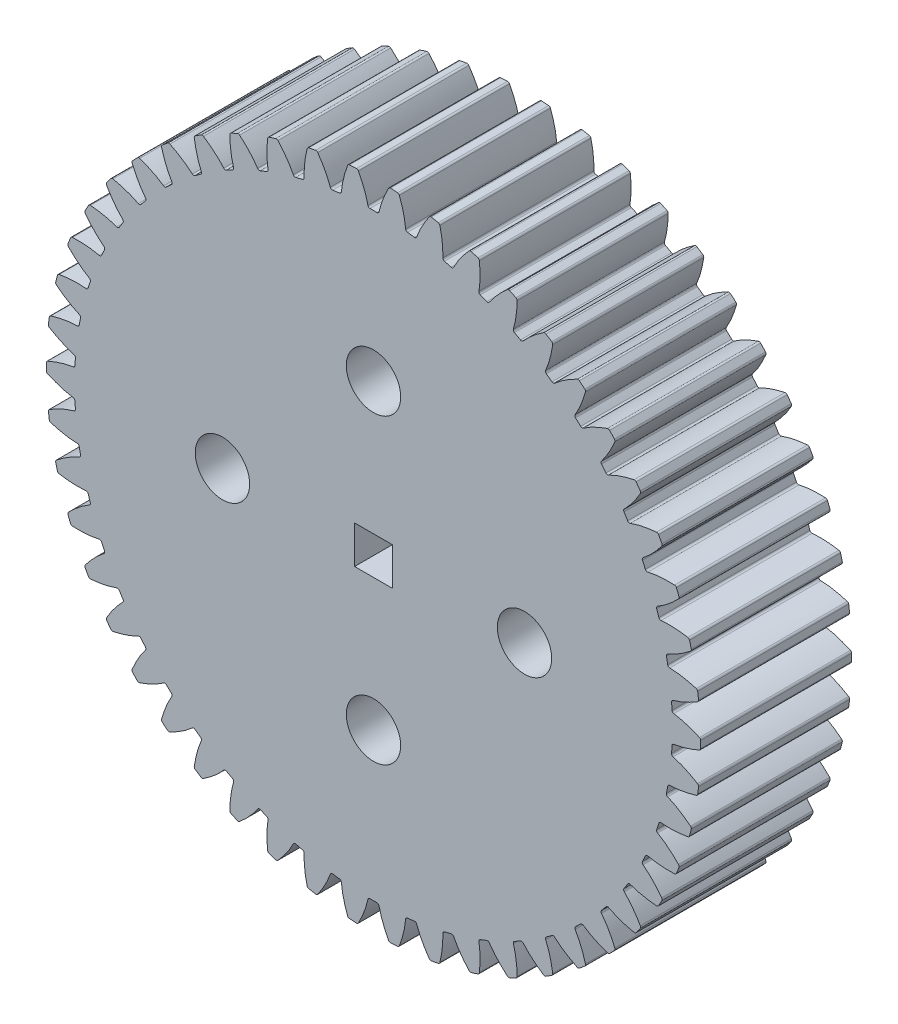
SolidWorks part; units mm, degrees
material "Alloy Steel"
ref_plane "Front" through (0, 0, 0) normal (0, 0, 1) x (1, 0, 0)
ref_plane "Top" through (0, 0, 0) normal (0, 1, 0) x (1, 0, 0)
ref_plane "Right" through (0, 0, 0) normal (1, 0, 0) x (0, 0, -1)
sketch "Sketch1" plane through (0, 0, 0) normal (0, 0, 1) x (1, 0, 0)
  circle A0 centre (0, 0) radius 27.5167
  dimension "OutsideDiameter" = 55.0333
extrude "Boss-Extrude1" add sketch "Sketch1" along normal blind 12.7
sketch "Sketch3" plane through (0, 0, 0) normal (0, 0, 1) x (1, 0, 0)
  line L0 (0, 0) -> (43.7181, 0) construction
  line L2 (0, 0) -> (-0.415, 25.132) construction
  line L3 (0, 0) -> (0.415, 25.132) construction
  line L4 (0.415, 25.132) -> (0.4105, 24.8593) construction
  line L5 (0, 0) -> (0, 61.276) construction
  line L6 (-0.415, 25.132) -> (-0.4105, 24.8593) construction
  circle A0 centre (0, 0) radius 27.5167 construction
  circle A1 centre (0, 0) radius 26.4583 construction
  circle A2 centre (0, 0) radius 24.8627 construction
  arc A3 (0.415, 25.132) -> (-0.415, 25.132) centre (0, 0) ccw construction
  arc A5 (1.3181, 27.4851) -> (-1.3181, 27.4851) centre (0, 0) ccw
  spline S0 degree 4 poles (-0.4105, 24.8593) (-0.4106, 24.8634) (-0.411, 24.875) (-0.4124, 24.8969) (-0.4153, 24.9326) (-0.42, 24.9781) (-0.4274, 25.0369) (-0.4376, 25.1061) (-0.4505, 25.182) (-0.4663, 25.2646) (-0.4836, 25.347) (-0.5023, 25.4291) (-0.5223, 25.5108) (-0.5481, 25.6097) (-0.5811, 25.7281) (-0.6229, 25.8665) (-0.674, 26.0231) (-0.7301, 26.1825) (-0.7886, 26.3392) (-0.8515, 26.4973) (-0.915, 26.65) (-0.9848, 26.8084) (-1.0512, 26.9545) (-1.13, 27.1178) (-1.1947, 27.2495) (-1.2847, 27.4229) (-1.3393, 27.5252) (-1.4047, 27.6448) (-1.4345, 27.6978) (-1.4529, 27.7305) knots 0 0 0 0 0 0.005377 0.015084 0.028532 0.04661 0.064855 0.092111 0.119476 0.146842 0.174209 0.201575 0.228941 0.256307 0.307035 0.361767 0.4165 0.471232 0.525964 0.580697 0.635429 0.690161 0.744894 0.799626 0.854358 0.909091 0.954545 1 1 1 1 1 construction
  spline S1 degree 4 poles (-0.4105, 24.8593) (-0.4106, 24.8634) (-0.411, 24.875) (-0.4124, 24.8969) (-0.4153, 24.9326) (-0.42, 24.9781) (-0.4274, 25.0369) (-0.4376, 25.1061) (-0.4505, 25.182) (-0.4663, 25.2646) (-0.4836, 25.347) (-0.5023, 25.4291) (-0.5223, 25.5108) (-0.5481, 25.6097) (-0.5811, 25.7281) (-0.6229, 25.8665) (-0.674, 26.0231) (-0.7301, 26.1825) (-0.7886, 26.3392) (-0.8515, 26.4973) (-0.915, 26.65) (-0.9848, 26.8084) (-1.0512, 26.9545) (-1.13, 27.1178) (-1.1947, 27.2495) (-1.2652, 27.3853) (-1.3001, 27.4513) (-1.3181, 27.4851) knots 0 0 0 0 0 0.005377 0.015084 0.028532 0.04661 0.064855 0.092111 0.119476 0.146842 0.174209 0.201575 0.228941 0.256307 0.307035 0.361767 0.4165 0.471232 0.525964 0.580697 0.635429 0.690161 0.744894 0.799626 0.854358 0.909091 0.909091 0.909091 0.909091 0.909091
  spline S2 degree 4 poles (0.4105, 24.8593) (0.4106, 24.8634) (0.411, 24.875) (0.4124, 24.8969) (0.4153, 24.9326) (0.42, 24.9781) (0.4274, 25.0369) (0.4376, 25.1061) (0.4505, 25.182) (0.4663, 25.2646) (0.4836, 25.347) (0.5023, 25.4291) (0.5223, 25.5108) (0.5481, 25.6097) (0.5811, 25.7281) (0.6229, 25.8665) (0.674, 26.0231) (0.7301, 26.1825) (0.7886, 26.3392) (0.8515, 26.4973) (0.915, 26.65) (0.9848, 26.8084) (1.0512, 26.9545) (1.13, 27.1178) (1.1947, 27.2495) (1.2847, 27.4229) (1.3393, 27.5252) (1.4047, 27.6448) (1.4345, 27.6978) (1.4529, 27.7305) knots 0 0 0 0 0 0.005377 0.015084 0.028532 0.04661 0.064855 0.092111 0.119476 0.146842 0.174209 0.201575 0.228941 0.256307 0.307035 0.361767 0.4165 0.471232 0.525964 0.580697 0.635429 0.690161 0.744894 0.799626 0.854358 0.909091 0.954545 1 1 1 1 1 construction
  spline S3 degree 4 poles (0.4105, 24.8593) (0.4106, 24.8634) (0.411, 24.875) (0.4124, 24.8969) (0.4153, 24.9326) (0.42, 24.9781) (0.4274, 25.0369) (0.4376, 25.1061) (0.4505, 25.182) (0.4663, 25.2646) (0.4836, 25.347) (0.5023, 25.4291) (0.5223, 25.5108) (0.5481, 25.6097) (0.5811, 25.7281) (0.6229, 25.8665) (0.674, 26.0231) (0.7301, 26.1825) (0.7886, 26.3392) (0.8515, 26.4973) (0.915, 26.65) (0.9848, 26.8084) (1.0512, 26.9545) (1.13, 27.1178) (1.1947, 27.2495) (1.2652, 27.3853) (1.3001, 27.4513) (1.3181, 27.4851) knots 0 0 0 0 0 0.005377 0.015084 0.028532 0.04661 0.064855 0.092111 0.119476 0.146842 0.174209 0.201575 0.228941 0.256307 0.307035 0.361767 0.4165 0.471232 0.525964 0.580697 0.635429 0.690161 0.744894 0.799626 0.854358 0.909091 0.909091 0.909091 0.909091 0.909091
  point P0 (0, 25.1354)
  dimension "OutsideDiameter" = 55.0333
  dimension "PitchCircle" = 52.9167
  dimension "BaseCircle" = 49.7254
  dimension "DedendumCircle" = 50.2708
sketch "DCLTBC" [suppressed] plane through (0, 0, 0) normal (0, 0, 1) x (1, 0, 0)
  line L0 (0, 0) -> (41.04, 0) construction
  line L1 (-0.5092, 17.7198) -> (-0.5142, 17.8938) construction
  line L2 (0.5092, 17.7198) -> (0.5142, 17.8938) construction
  line L3 (-0.5092, 17.7198) -> (-0.5142, 17.8938)
  line L4 (0.5092, 17.7198) -> (0.5142, 17.8938)
  line L5 (0, 0) -> (0, 104.9356) construction
  circle A0 centre (0, 0) radius 20.1083
  circle A1 centre (0, 0) radius 19.05 construction
  circle A2 centre (0, 0) radius 17.9011 construction
  arc A3 (0.5092, 17.7198) -> (-0.5092, 17.7198) centre (0, 0) ccw construction
  arc A4 (0.5092, 17.7198) -> (-0.5092, 17.7198) centre (0, 0) ccw
  spline S0 degree 4 poles (-999.1216, -34.2256) (-11.697, 16.348) (-0.6508, 17.0677) (-0.4759, 17.5158) (-0.5192, 17.9552) (-0.5239, 17.9932) (-0.5311, 18.0423) (-0.541, 18.1001) (-0.5533, 18.1635) (-0.5683, 18.2324) (-0.5847, 18.3009) (-0.6024, 18.3693) (-0.6212, 18.4372) (-0.6453, 18.5194) (-0.6762, 18.6178) (-0.7152, 18.7324) (-0.7627, 18.8621) (-0.8147, 18.9939) (-0.8688, 19.1232) (-0.9269, 19.2534) (-0.9855, 19.3791) (-1.0497, 19.5092) (-1.1108, 19.629) (-1.1831, 19.7627) (-1.4901, 20.3193) (-2.6416, 22.1387) (11.7833, -2.0901) (-516.0573, 877.426) knots -0.638399 -0.638399 -0.638399 -0.638399 -0.638399 0.005377 0.015084 0.028532 0.04661 0.064855 0.092111 0.119476 0.146842 0.174209 0.201575 0.228941 0.256307 0.307035 0.361767 0.4165 0.471232 0.525964 0.580697 0.635429 0.690161 0.744894 0.799626 0.854358 1.821345 1.821345 1.821345 1.821345 1.821345 only from (-0.5142, 17.8938) to (-1.3554, 20.0626) construction
  spline S1 degree 4 poles (999.1216, -34.2256) (11.697, 16.348) (0.6508, 17.0677) (0.4759, 17.5158) (0.5192, 17.9552) (0.5239, 17.9932) (0.5311, 18.0423) (0.541, 18.1001) (0.5533, 18.1635) (0.5683, 18.2324) (0.5847, 18.3009) (0.6024, 18.3693) (0.6212, 18.4372) (0.6453, 18.5194) (0.6762, 18.6178) (0.7152, 18.7324) (0.7627, 18.8621) (0.8147, 18.9939) (0.8688, 19.1232) (0.9269, 19.2534) (0.9855, 19.3791) (1.0497, 19.5092) (1.1108, 19.629) (1.1831, 19.7627) (1.4901, 20.3193) (2.6416, 22.1387) (-11.7833, -2.0901) (516.0573, 877.426) knots -0.638399 -0.638399 -0.638399 -0.638399 -0.638399 0.005377 0.015084 0.028532 0.04661 0.064855 0.092111 0.119476 0.146842 0.174209 0.201575 0.228941 0.256307 0.307035 0.361767 0.4165 0.471232 0.525964 0.580697 0.635429 0.690161 0.744894 0.799626 0.854358 1.821345 1.821345 1.821345 1.821345 1.821345 only from (0.5142, 17.8938) to (1.3554, 20.0626) construction
  spline S2 degree 4 poles (-0.5142, 17.8938) (-0.5143, 17.8972) (-0.5148, 17.9069) (-0.5163, 17.9253) (-0.5192, 17.9552) (-0.5239, 17.9932) (-0.5311, 18.0423) (-0.541, 18.1001) (-0.5533, 18.1635) (-0.5683, 18.2324) (-0.5847, 18.3009) (-0.6024, 18.3693) (-0.6212, 18.4372) (-0.6453, 18.5194) (-0.6762, 18.6178) (-0.7152, 18.7324) (-0.7627, 18.8621) (-0.8147, 18.9939) (-0.8688, 19.1232) (-0.9269, 19.2534) (-0.9855, 19.3791) (-1.0497, 19.5092) (-1.1108, 19.629) (-1.1831, 19.7627) (-1.2425, 19.8704) (-1.307, 19.9812) (-1.3389, 20.0351) (-1.3554, 20.0626) knots 0 0 0 0 0 0.005377 0.015084 0.028532 0.04661 0.064855 0.092111 0.119476 0.146842 0.174209 0.201575 0.228941 0.256307 0.307035 0.361767 0.4165 0.471232 0.525964 0.580697 0.635429 0.690161 0.744894 0.799626 0.854358 0.909091 0.909091 0.909091 0.909091 0.909091
  spline S3 degree 4 poles (0.5142, 17.8938) (0.5143, 17.8972) (0.5148, 17.9069) (0.5163, 17.9253) (0.5192, 17.9552) (0.5239, 17.9932) (0.5311, 18.0423) (0.541, 18.1001) (0.5533, 18.1635) (0.5683, 18.2324) (0.5847, 18.3009) (0.6024, 18.3693) (0.6212, 18.4372) (0.6453, 18.5194) (0.6762, 18.6178) (0.7152, 18.7324) (0.7627, 18.8621) (0.8147, 18.9939) (0.8688, 19.1232) (0.9269, 19.2534) (0.9855, 19.3791) (1.0497, 19.5092) (1.1108, 19.629) (1.1831, 19.7627) (1.2425, 19.8704) (1.307, 19.9812) (1.3389, 20.0351) (1.3554, 20.0626) knots 0 0 0 0 0 0.005377 0.015084 0.028532 0.04661 0.064855 0.092111 0.119476 0.146842 0.174209 0.201575 0.228941 0.256307 0.307035 0.361767 0.4165 0.471232 0.525964 0.580697 0.635429 0.690161 0.744894 0.799626 0.854358 0.909091 0.909091 0.909091 0.909091 0.909091
  dimension "OutsideDiameter" = 55.0333
  dimension "PitchCircle" = 52.9167
  dimension "BaseCircle" = 49.7254
extrude "Cut-Extrude-DCLTBC" [suppressed] cut sketch "DCLTBC" along normal through all
fillet "Fillet-Tip-DCLTBC" [suppressed] radius 0.1775
fillet "Fillet-Root-DCLTBC" [suppressed] radius 0.3551
pattern_circular "CirPattern-DCLTBC" [suppressed] count 50 over 360 of bodies 111
sketch "DCGTBC" plane through (0, 0, 0) normal (0, 0, 1) x (1, 0, 0)
  line L0 (0, 0) -> (41.04, 0) construction
  line L1 (-25.0398, 2.1907) -> (0, 0) construction
  line L2 (0, 0) -> (25.0398, 2.1907) construction
  line L3 (0, 0) -> (-16.5124, 0)
  line L5 (0, 0) -> (0, 104.9356) construction
  circle A0 centre (0, 0) radius 27.5167
  circle A1 centre (0, 0) radius 26.4583 construction
  circle A2 centre (0, 0) radius 24.8627 construction
  arc A3 (0.415, 25.132) -> (-0.415, 25.132) centre (0, 0) ccw construction
  arc A11 (25.0398, 2.1907) -> (-25.0398, 2.1907) centre (0, 0) ccw
  spline S4 degree 4 poles (999.5065, -17.4772) (11.9082, 23.2518) (0.562, 23.9037) (0.3737, 24.4201) (0.4153, 24.9326) (0.42, 24.9781) (0.4274, 25.0369) (0.4376, 25.1061) (0.4505, 25.182) (0.4663, 25.2646) (0.4836, 25.347) (0.5023, 25.4291) (0.5223, 25.5108) (0.5481, 25.6097) (0.5811, 25.7281) (0.6229, 25.8665) (0.674, 26.0231) (0.7301, 26.1825) (0.7886, 26.3392) (0.8515, 26.4973) (0.915, 26.65) (0.9848, 26.8084) (1.0512, 26.9545) (1.13, 27.1178) (1.4526, 27.7739) (2.631, 29.8694) (-11.2314, 3.719) (472.8115, 909.3101) knots -0.622238 -0.622238 -0.622238 -0.622238 -0.622238 0.005377 0.015084 0.028532 0.04661 0.064855 0.092111 0.119476 0.146842 0.174209 0.201575 0.228941 0.256307 0.307035 0.361767 0.4165 0.471232 0.525964 0.580697 0.635429 0.690161 0.744894 0.799626 0.854358 1.780642 1.780642 1.780642 1.780642 1.780642 only from (0.4105, 24.8593) to (1.3181, 27.4851) construction
  spline S5 degree 4 poles (-999.5065, -17.4771) (-11.9082, 23.2518) (-0.562, 23.9037) (-0.3737, 24.4201) (-0.4153, 24.9326) (-0.42, 24.9781) (-0.4274, 25.0369) (-0.4376, 25.1061) (-0.4505, 25.182) (-0.4663, 25.2646) (-0.4836, 25.347) (-0.5023, 25.4291) (-0.5223, 25.5108) (-0.5481, 25.6097) (-0.5811, 25.7281) (-0.6229, 25.8665) (-0.674, 26.0231) (-0.7301, 26.1825) (-0.7886, 26.3392) (-0.8515, 26.4973) (-0.915, 26.65) (-0.9848, 26.8084) (-1.0512, 26.9545) (-1.13, 27.1178) (-1.4526, 27.7739) (-2.631, 29.8694) (11.2314, 3.719) (-472.8115, 909.3101) knots -0.622238 -0.622238 -0.622238 -0.622238 -0.622238 0.005377 0.015084 0.028532 0.04661 0.064855 0.092111 0.119476 0.146842 0.174209 0.201575 0.228941 0.256307 0.307035 0.361767 0.4165 0.471232 0.525964 0.580697 0.635429 0.690161 0.744894 0.799626 0.854358 1.780642 1.780642 1.780642 1.780642 1.780642 only from (-0.4105, 24.8593) to (-1.3181, 27.4851) construction
  spline S6 degree 4 poles (0.4105, 24.8593) (0.4106, 24.8634) (0.411, 24.875) (0.4124, 24.8969) (0.4153, 24.9326) (0.42, 24.9781) (0.4274, 25.0369) (0.4376, 25.1061) (0.4505, 25.182) (0.4663, 25.2646) (0.4836, 25.347) (0.5023, 25.4291) (0.5223, 25.5108) (0.5481, 25.6097) (0.5811, 25.7281) (0.6229, 25.8665) (0.674, 26.0231) (0.7301, 26.1825) (0.7886, 26.3392) (0.8515, 26.4973) (0.915, 26.65) (0.9848, 26.8084) (1.0512, 26.9545) (1.13, 27.1178) (1.1947, 27.2495) (1.2652, 27.3853) (1.3001, 27.4513) (1.3181, 27.4851) knots 0 0 0 0 0 0.005377 0.015084 0.028532 0.04661 0.064855 0.092111 0.119476 0.146842 0.174209 0.201575 0.228941 0.256307 0.307035 0.361767 0.4165 0.471232 0.525964 0.580697 0.635429 0.690161 0.744894 0.799626 0.854358 0.909091 0.909091 0.909091 0.909091 0.909091
  spline S7 degree 4 poles (-0.4105, 24.8593) (-0.4106, 24.8634) (-0.411, 24.875) (-0.4124, 24.8969) (-0.4153, 24.9326) (-0.42, 24.9781) (-0.4274, 25.0369) (-0.4376, 25.1061) (-0.4505, 25.182) (-0.4663, 25.2646) (-0.4836, 25.347) (-0.5023, 25.4291) (-0.5223, 25.5108) (-0.5481, 25.6097) (-0.5811, 25.7281) (-0.6229, 25.8665) (-0.674, 26.0231) (-0.7301, 26.1825) (-0.7886, 26.3392) (-0.8515, 26.4973) (-0.915, 26.65) (-0.9848, 26.8084) (-1.0512, 26.9545) (-1.13, 27.1178) (-1.1947, 27.2495) (-1.2652, 27.3853) (-1.3001, 27.4513) (-1.3181, 27.4851) knots 0 0 0 0 0 0.005377 0.015084 0.028532 0.04661 0.064855 0.092111 0.119476 0.146842 0.174209 0.201575 0.228941 0.256307 0.307035 0.361767 0.4165 0.471232 0.525964 0.580697 0.635429 0.690161 0.744894 0.799626 0.854358 0.909091 0.909091 0.909091 0.909091 0.909091
  dimension "D1" = 5
  dimension "D2" = 5
  dimension "OutsideDiameter" = 55.0333
  dimension "PitchCircle" = 52.9167
  dimension "BaseCircle" = 49.7254
extrude "Cut-Extrude-DCGTBC" cut sketch "DCGTBC" along normal through all contours A0 A11 region at (0, 26.5371, 0)
fillet "Fillet-Tip-DCGTBC" radius 0.1775 4 edges at (1.3181, 27.4851, 6.35) (-1.3181, 27.4851, 6.35) (0.4421, 25.1315, 6.35) (-0.4421, 25.1315, 6.35)
pattern_circular "CirPattern-DCGTBC" count 50 over 360 about axis through (0, 0, 12.7) along (0, 0, 1) of "Cut-Extrude-DCGTBC", "Fillet-Tip-DCGTBC"
sketch "Sketch4" plane through (0, 0, 12.7) normal (0, 0, 1) x (1, 0, 0)
  line L1 (-1.5875, -1.5875) -> (1.5875, -1.5875)
  line L2 (-1.5875, -1.5875) -> (-1.5875, 1.5875)
  line L3 (-1.5875, 1.5875) -> (1.5875, 1.5875)
  line L4 (1.5875, -1.5875) -> (1.5875, 1.5875)
  line L5 (-1.5875, -1.5875) -> (1.5875, 1.5875) construction
  line L6 (-1.5875, 1.5875) -> (1.5875, -1.5875) construction
  point P0 (0, 0)
  dimension "D1" = 3.175
extrude "Cut-Extrude2" cut sketch "Sketch4" against normal through all
sketch "Sketch5" plane through (0, 0, 12.7) normal (0, 0, 1) x (1, 0, 0)
  circle A0 centre (-12.7, 0) radius 2.286
  circle A1 centre (0, 12.7) radius 2.286
  circle A2 centre (12.7, 0) radius 2.286
  circle A3 centre (0, -12.7) radius 2.286
  point P12 (0, 0)
  dimension "D2" = 4.572
  dimension "D1" = 12.7
  dimension "D3" = 4
extrude "Cut-Extrude3" cut sketch "Sketch5" against normal through all
equation "\"DiametralPitch\"= 24'Diametral Pitch"
equation "\"NumTeeth\"= 50'Number of Teeth"
equation "\"PressureAngle\"= 20deg'Pressure Angle"
equation "\"Addendum\"= 1 / \"DiametralPitch\"'Addendum"
equation "\"Dedendum\"= 1.25 / \"DiametralPitch\"'Dedendum"
equation "\"WorkingDepth\"= 2 / \"DiametralPitch\"'Working Depth - here for REF (Not used in building model)"
equation "\"WholeDepth\"= 2.25 / \"DiametralPitch\"'Whole Depth - here for REF (Not used in building model)"
equation "\"Clearance\"= .25 / \"DiametralPitch\"'Clearance"
equation "\"CircularPitch\"= pi / \"DiametralPitch\"'Circular Pitch - here for REF (Not used in building model)"
equation "\"PitchCircle\"= \"NumTeeth\" / \"DiametralPitch\"'Pitch Circle - or - Pitch Diameter"
equation "\"OutsideDiameter\"= ( \"NumTeeth\" + 2 ) / \"DiametralPitch\"'Outside Diameter"
equation "\"Fillet_Root\"= \"Clearance\" * cos ( \"PressureAngle\" ) * tan ( ( 90 + \"PressureAngle\" ) / 2 ) 'Fillet Root"
equation "\"AddendumCircle\"= \"PitchCircle\" + ( 2 * \"Addendum\" )'Addendum Circle - or - Addendum Diameter"
equation "\"DedendumCircle\"= \"PitchCircle\" - ( 2 * \"Dedendum\" )'Dedendum Circle - or - Dedendum Diameter"
equation "\"BaseCircle\"= \"PitchCircle\" * cos ( \"PressureAngle\" )'Base Circle - Base Diameter"
equation "\"PitchAngle\"= 360deg / \"NumTeeth\"'Pitch Angle"
equation "\"Alpha\"= sqr ( \"PitchCircle\" ^ 2 - \"BaseCircle\" ^ 2 ) / \"BaseCircle\" * 180 / PI - \"PressureAngle\"'Alpha - Used for Calculating Beta"
equation "\"Beta\"= ( \"PitchAngle\" / 4 - ( \"Alpha\" - 90 ) )'Beta - Used in definition of the parameters for the parametric equation driven curve"
equation "\"Gamma\"= ( \"PitchAngle\" / 4 - ( \"Alpha\" + 90 ) )'Gamma - Used in definition of the parameters for the parametric equation driven curve"
equation "\"Phi\"= sqr ( ( \"AddendumCircle\" / 2 ) ^ 2 - ( \"BaseCircle\" / 2 ) ^ 2 ) / ( \"BaseCircle\" / 2 )'Phi - Used in definition of the parameters for the parametric equation driven curve"
equation "\"DCGTBC\"= iif ( \"DedendumCircle\" > \"BaseCircle\" , \"unsuppressed\" , \"suppressed\" )'if Dedendum Circle IS GREATER THAN BaseCircle THEN UnsuppressORSuppress FEATURE"
equation "\"DCLTBC\"= iif ( \"DedendumCircle\" - .002 > \"BaseCircle\" , \"suppressed\" , \"unsuppressed\" )'if Dedendum Circle - .002 IS GREATER THAN BaseCircle THEN SuppressORUnsuppress FEATURE"
equation "\"Cut-Extrude-DCGTBC\"= iif ( \"DedendumCircle\" > \"BaseCircle\" , \"unsuppressed\" , \"suppressed\" )'if Dedendum Circle IS GREATER THAN BaseCircle THEN UnsuppressORSuppress FEATURE"
equation "\"Cut-Extrude-DCLTBC\"= iif ( \"DedendumCircle\" - .002 > \"BaseCircle\" , \"suppressed\" , \"unsuppressed\" )'if Dedendum Circle - .002 IS GREATER THAN BaseCircle THEN SuppressORUnsuppress FEATURE"
equation "\"CirPattern-DCGTBC\"= iif ( \"DedendumCircle\" > \"BaseCircle\" , \"unsuppressed\" , \"suppressed\" )'if Dedendum Circle IS GREATER THAN BaseCircle THEN UnsuppressORSuppress FEATURE"
equation "\"CirPattern-DCLTBC\"= iif ( \"DedendumCircle\" - .002 > \"BaseCircle\" , \"suppressed\" , \"unsuppressed\" )'if Dedendum Circle - .002 IS GREATER THAN BaseCircle THEN SuppressORUnsuppress FEATURE"
equation "\"Fillet-Tip-DCGTBC\"= iif ( \"DedendumCircle\" > \"BaseCircle\" , \"unsuppressed\" , \"suppressed\" )'if Dedendum Circle IS GREATER THAN BaseCircle THEN UnsuppressORSuppress FEATURE"
equation "\"Fillet-Tip-DCLTBC\"= iif ( \"DedendumCircle\" - .002 > \"BaseCircle\" , \"suppressed\" , \"unsuppressed\" )'if Dedendum Circle - .002 IS GREATER THAN BaseCircle THEN SuppressORUnsuppress FEATURE"
equation "\"Fillet-Root-DCLTBC\"= iif ( \"DedendumCircle\" - .002 > \"BaseCircle\" , \"suppressed\" , \"unsuppressed\" )'if Dedendum Circle - .002 IS GREATER THAN BaseCircle THEN SuppressORUnsuppress FEATURE"
equation "\"D1@CirPattern-DCGTBC\"= \"NumTeeth\"'Number of Teeth"
equation "\"D1@CirPattern-DCLTBC\"= \"NumTeeth\"'Number of Teeth"
equation "\"D1@Fillet-Tip-DCGTBC\"= \"Fillet_Root\" / 2 'Tip Rad For Large No of Teeth"
equation "\"D1@Fillet-Tip-DCLTBC\"=\"Fillet_Root\" / 2'Tip Rad For Small No of Teeth"
equation "\"D1@Fillet-Root-DCLTBC\"= \"Fillet_Root\"'Fillet Root"
